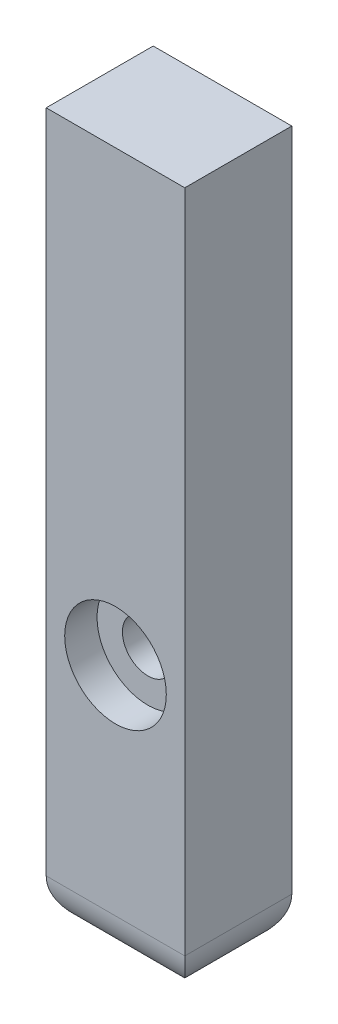
SolidWorks part; units mm, degrees
ref_plane "Front Plane" through (0, 0, 0) normal (0, 0, 1) x (1, 0, 0)
ref_plane "Top Plane" through (0, 0, 0) normal (0, 1, 0) x (1, 0, 0)
ref_plane "Right Plane" through (0, 0, 0) normal (1, 0, 0) x (0, 0, -1)
sketch "Sketch1" plane through (0, 0, 0) normal (0, 0, 1) x (1, 0, 0)
  line L0 (-15, -17) -> (0, 0) construction
  line L1 (-15, 57.0003) -> (15, 57.0003)
  line L2 (-15, 57.0003) -> (-15, -17)
  line L3 (-15, -17) -> (15, -17)
  line L4 (15, 57.0003) -> (15, -17)
  line L5 (0, 0) -> (15, -17) construction
  line L6 (-15, 57.0003) -> (0, 40.0003) construction
  line L7 (0, 40.0003) -> (15, 57.0003) construction
  circle A0 centre (0, 0) radius 7.9823
  circle A1 centre (0, 40.0003) radius 11
  dimension "D3" = 30
  dimension "D4" = 22
  dimension "D5" = 15.9646
  dimension "D1" = 40.0003
  dimension "D2" = 17
extrude "Boss-Extrude1" add sketch "Sketch1" along normal blind 23.1638
sketch "Sketch2" plane through (0, 0, 23.1638) normal (0, 0, 1) x (1, 0, 0)
  circle A0 centre (0, 0) radius 4
  circle A1 centre (0, 0) radius 7.9823 construction
  circle A2 centre (0, 0) radius 7.9823
  dimension "D1" = 8
extrude "Boss-Extrude2" add sketch "Sketch2" against normal up to surface (23.1638 mm away) up to face at (0, 20.0001, 0)
sketch "Sketch3" plane through (0, 0, 23.1638) normal (0, 0, 1) x (1, 0, 0)
  circle A0 centre (0, 0) radius 4
extrude "Boss-Extrude3" add sketch "Sketch3" against normal blind 32.1638
sketch "Sketch4" plane through (0, 0, 0) normal (0, 0, -1) x (-1, 0, 0)
  circle A0 centre (0, 40.0003) radius 11 construction
  circle A1 centre (0, 40.0003) radius 11
  circle A2 centre (0, 40.0003) radius 5.5
  dimension "D1" = 5.5
extrude "Boss-Extrude4" add sketch "Sketch4" against normal blind 16.1638
fillet "Fillet1" radius 10 4 edges at (-15, -17, 11.5819) (0, -17, 23.1638) (15, -17, 11.5819) (0, -17, 0)
sketch "Sketch5" plane through (0, 0, 23.1638) normal (0, 0, 1) x (1, 0, 0)
  line L0 (15, -7) -> (15, 57.0003) construction
  line L1 (-15, 57.0003) -> (15, 57.0003)
  line L2 (-15, 57.0003) -> (-15, 137.0003)
  line L3 (-15, 137.0003) -> (15, 137.0003)
  line L4 (15, 57.0003) -> (15, 137.0003)
  dimension "D1" = 80
extrude "Boss-Extrude5" add sketch "Sketch5" against normal up to surface (23.1638 mm away) up to face at (0, 25.0001, 0)
